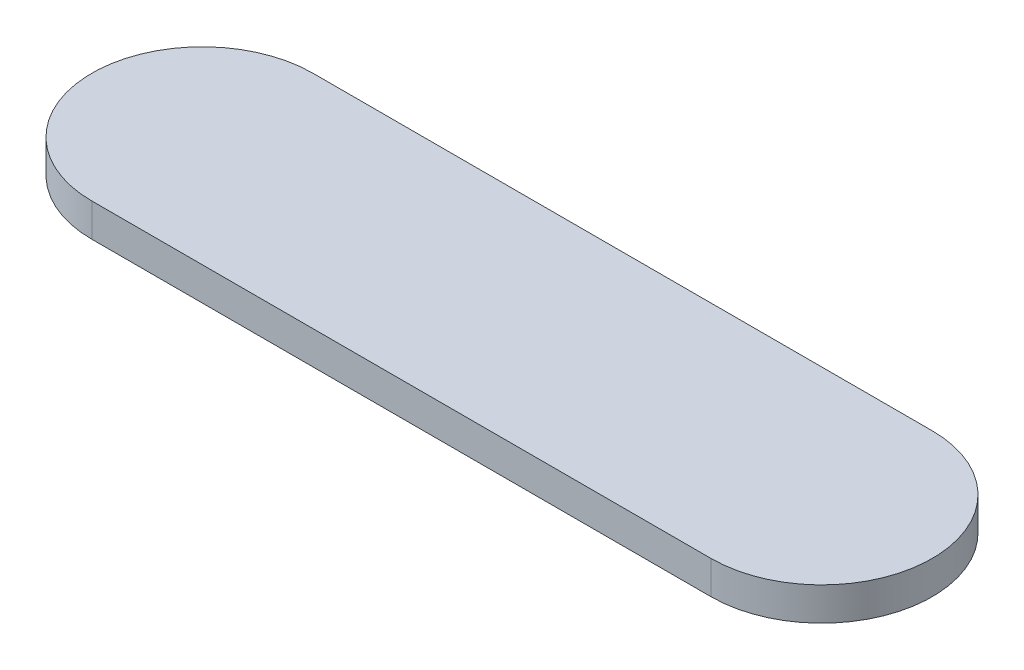
SolidWorks part; units mm, degrees
ref_plane "Front Plane" through (0, 0, 0) normal (0, 0, 1) x (1, 0, 0)
ref_plane "Top Plane" through (0, 0, 0) normal (0, 1, 0) x (1, 0, 0)
ref_plane "Right Plane" through (0, 0, 0) normal (1, 0, 0) x (0, 0, -1)
sketch "Sketch2" plane through (0, 0, 0) normal (0, 1, 0) x (1, 0, 0)
  line L0 (42, 0) -> (-42, 0) construction
  line L1 (42, 15) -> (-42, 15)
  line L2 (42, -15) -> (-42, -15)
  arc A0 (42, 15) -> (42, -15) centre (42, 0) cw
  arc A1 (-42, 15) -> (-42, -15) centre (-42, 0) ccw
  point P4 (0, 0)
  dimension "D1" = 84
  dimension "D2" = 15
  dimension "D3" = 15
extrude "Boss-Extrude1" add sketch "Sketch2" along normal blind 4.5
